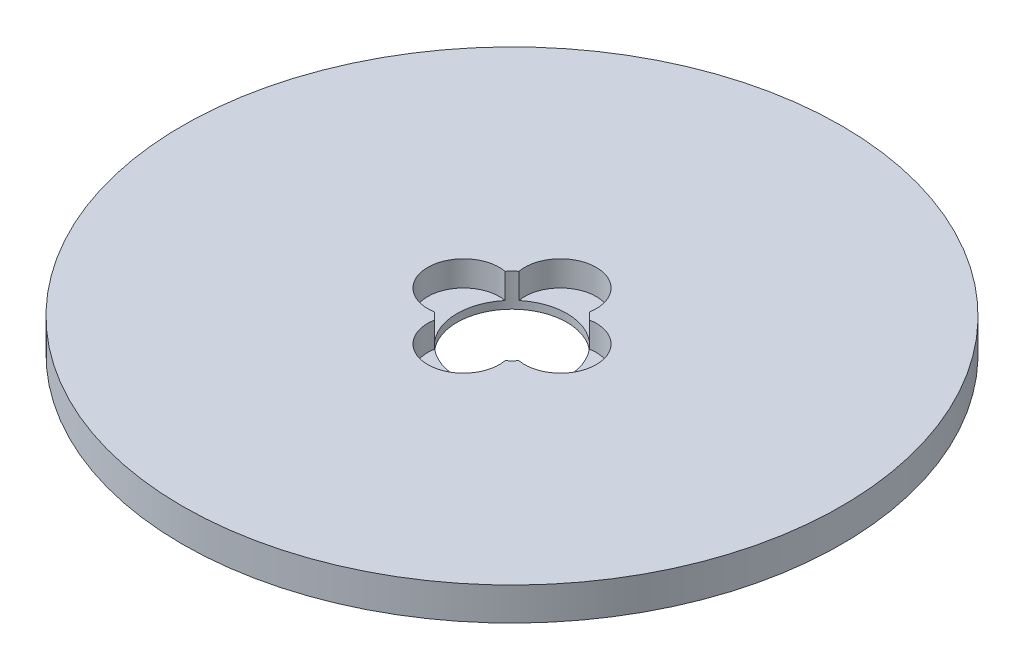
SolidWorks part; units mm, degrees
ref_plane "Front Plane" through (0, 0, 0) normal (0, 0, 1) x (1, 0, 0)
ref_plane "Top Plane" through (0, 0, 0) normal (0, 1, 0) x (1, 0, 0)
ref_plane "Right Plane" through (0, 0, 0) normal (1, 0, 0) x (0, 0, -1)
sketch "Sketch1" plane through (0, 0, 0) normal (0, 1, 0) x (1, 0, 0)
  circle A0 centre (0, 0) radius 90
  dimension "FLANGE_OD" = 180
extrude "Boss-Extrude1" add sketch "Sketch1" along normal blind 9
sketch "Sketch2" plane through (0, 0, 0) normal (0, 1, 0) x (1, 0, 0)
  circle A0 centre (0, 0) radius 15
  dimension "BORE_D" = 30
extrude "Cut-Extrude1" cut sketch "Sketch2" along normal through all
sketch "Sketch3" plane through (0, 9, 0) normal (0, 1, 0) x (1, 0, 0)
  circle A0 centre (0, 0) radius 13.231 construction
  circle A1 centre (-13.231, 0) radius 9.781
  dimension "BOLT_D" = 19.562
  dimension "BOLT_PCD" = 26.462
extrude "Cut-Extrude2" cut sketch "Sketch3" against normal blind 6.906
pattern_circular "CirPattern1" count 4 over 360 about axis through (0, 0, 0) along (0, 1, 0) of "Cut-Extrude2"
